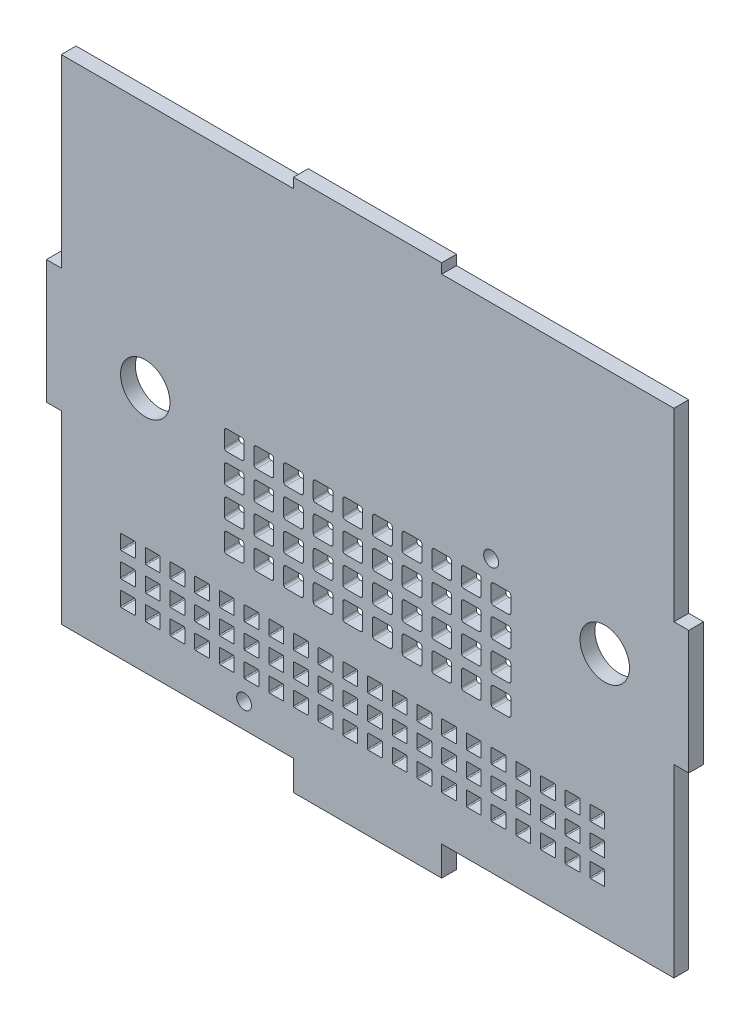
SolidWorks part; units mm, degrees
ref_plane "Front Plane" through (0, 0, 0) normal (0, 0, 1) x (1, 0, 0)
ref_plane "Top Plane" through (0, 0, 0) normal (0, 1, 0) x (1, 0, 0)
ref_plane "Right Plane" through (0, 0, 0) normal (1, 0, 0) x (0, 0, -1)
sketch "Sketch1" plane through (0, 0, 0) normal (0, 0, 1) x (1, 0, 0)
  line L0 (0, 0) -> (47, 0)
  line L1 (47, 0) -> (47, -6)
  line L2 (47, -6) -> (77, -6)
  line L3 (77, -6) -> (77, 0)
  line L4 (77, 0) -> (124, 0)
  line L5 (124, 0) -> (124, 37.43)
  line L6 (124, 37.43) -> (127, 37.43)
  line L7 (127, 37.43) -> (127, 62.43)
  line L8 (127, 62.43) -> (124, 62.43)
  line L9 (124, 62.43) -> (124, 99.86)
  line L10 (124, 99.86) -> (77, 99.86)
  line L11 (77, 99.86) -> (77, 101.86)
  line L12 (77, 101.86) -> (47, 101.86)
  line L13 (47, 101.86) -> (47, 99.86)
  line L14 (47, 99.86) -> (0, 99.86)
  line L15 (0, 99.86) -> (0, 62.43)
  line L16 (0, 62.43) -> (-3, 62.43)
  line L17 (-3, 62.43) -> (-3, 37.43)
  line L18 (-3, 37.43) -> (0, 37.43)
  line L19 (0, 37.43) -> (0, 0)
  dimension "D1" = 124
  dimension "D2" = 30
  dimension "D3" = 6
  dimension "D4" = 99.86
  dimension "D5" = 25
  dimension "D6" = 3
  dimension "D7" = 2
  dimension "D8" = 30
extrude "Boss-Extrude1" add sketch "Sketch1" along normal blind 3
sketch "Sketch2" plane through (0, 0, 3) normal (0, 0, 1) x (1, 0, 0)
  line L0 (0, 37.43) -> (0, 0) construction
  line L1 (0, 0) -> (47, 0) construction
  circle A0 centre (87, 55) radius 1.5
  circle A1 centre (37, 5) radius 1.5
  dimension "D1" = 3
  dimension "D2" = 50
  dimension "D3" = 50
  dimension "D4" = 37
  dimension "D5" = 5
extrude "Cut-Extrude1" cut sketch "Sketch2" against normal through all
sketch "Sketch3" plane through (0, 0, 3) normal (0, 0, 1) x (1, 0, 0)
  line L1 (0, 37.43) -> (0, 0) construction
  line L3 (47, 99.86) -> (0, 99.86) construction
  line L18 (127, 37.43) -> (127, 62.43) construction
  circle A2 centre (17, 49.86) radius 5
  circle A3 centre (110, 49.86) radius 5
  dimension "D1" = 10
  dimension "D2" = 17
  dimension "D3" = 50
  dimension "D4" = 17
extrude "Cut-Extrude2" cut sketch "Sketch3" against normal through all
sketch "Sketch4" plane through (0, 0, 3) normal (0, 0, 1) x (1, 0, 0)
  line L1 (33.5, 51) -> (36.5, 51)
  line L2 (33, 50.5) -> (33, 47.5)
  line L3 (33.5, 47) -> (36.5, 47)
  line L4 (37, 50.5) -> (37, 47.5)
  line L13 (0, 37.43) -> (0, 0) construction
  arc A0 (36.5, 51) -> (37, 50.5) centre (36.5, 50.5) cw
  arc A1 (36.5, 47) -> (37, 47.5) centre (36.5, 47.5) ccw
  arc A2 (33, 47.5) -> (33.5, 47) centre (33.5, 47.5) ccw
  arc A3 (33.5, 51) -> (33, 50.5) centre (33.5, 50.5) ccw
  circle A4 centre (87, 55) radius 1.5 construction
  point P6 (37, 51)
  point P11 (33, 47)
  point P14 (33, 51)
  dimension "D3" = 0.5
  dimension "D1" = 4
  dimension "D2" = 4
  dimension "D10" = 4
  dimension "D11" = 33
extrude "Cut-Extrude3" cut sketch "Sketch4" against normal through all
pattern_linear "LPattern1" count 4 spacing 6 along (0, -1, 0) count 10 spacing 6 along (1, 0, 0) of "Cut-Extrude3"
sketch "Sketch5" plane through (0, 0, 3) normal (0, 0, 1) x (1, 0, 0)
  line L0 (0, 37.43) -> (0, 0) construction
  line L2 (12.2, 12) -> (14.8, 12)
  line L3 (12, 11.8) -> (12, 9.2)
  line L4 (12.2, 9) -> (14.8, 9)
  line L5 (15, 11.8) -> (15, 9.2)
  arc A0 (12, 9.2) -> (12.2, 9) centre (12.2, 9.2) ccw
  arc A2 (14.8, 9) -> (15, 9.2) centre (14.8, 9.2) ccw
  arc A3 (14.8, 12) -> (15, 11.8) centre (14.8, 11.8) cw
  arc A4 (12.2, 12) -> (12, 11.8) centre (12.2, 11.8) ccw
  circle A6 centre (37, 5) radius 1.5 construction
  point P6 (12, 9)
  point P11 (15, 12)
  point P14 (12, 12)
  dimension "D1" = 3
  dimension "D4" = 12
  dimension "D3" = 0.2
  dimension "D2" = 3
  dimension "D5" = 4
extrude "Cut-Extrude4" cut sketch "Sketch5" against normal through all
pattern_linear "LPattern2" count 3 spacing 5 along (0, 1, 0) count 20 spacing 5 along (1, 0, 0) of "Cut-Extrude4"
